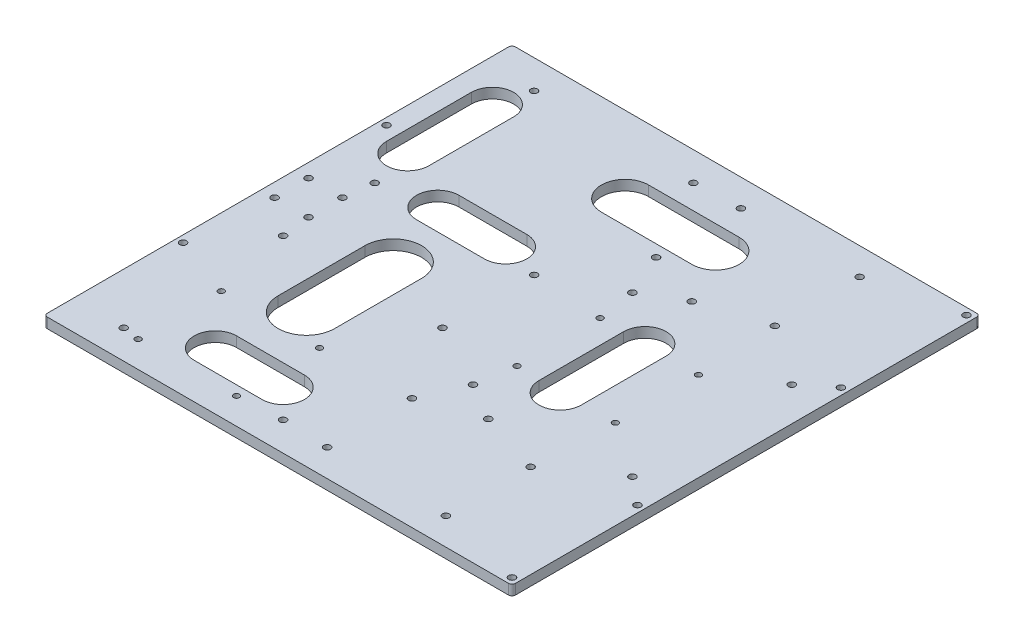
SolidWorks part; units mm, degrees
ref_plane "Спереди" through (0, 0, 0) normal (0, 0, 1) x (1, 0, 0)
ref_plane "Сверху" through (0, 0, 0) normal (0, 1, 0) x (1, 0, 0)
ref_plane "Справа" through (0, 0, 0) normal (1, 0, 0) x (0, 0, -1)
sketch "Эскиз1" plane through (0, 0, 0) normal (0, 1, 0) x (1, 0, 0)
  line L1 (-138, -138) -> (138, -138)
  line L2 (-138, -138) -> (-138, 138)
  line L3 (-138, 138) -> (138, 138)
  line L4 (138, -138) -> (138, 138)
  line L5 (0, 138) -> (0, -138) construction
  line L6 (-138, 0) -> (138, 0) construction
  point P0 (0, 0)
  dimension "D1" = 276
  dimension "D2" = 276
extrude "Бобышка-Вытянуть1" add sketch "Эскиз1" along normal blind 6
fillet "Скругление1" radius 2 4 edges at (138, 3, 138) (-138, 3, 138) (-138, 3, -138) (138, 3, -138)
sketch "Эскиз2" plane through (0, 6, 0) normal (0, 1, 0) x (1, 0, 0)
  line L0 (0, 147.7994) -> (0, 0) construction
  line L1 (0, 0) -> (-164.0684, 0) construction
  line L2 (-164.0684, 0) -> (215.1731, 0) construction
  circle A0 centre (-134, 60) radius 2
  circle A1 centre (134, 60) radius 2
  circle A2 centre (134, -60) radius 2
  circle A3 centre (-134, -60) radius 2
  circle A4 centre (46, 60) radius 2
  circle A5 centre (46, -60) radius 2
  circle A6 centre (134, 134) radius 2
  circle A7 centre (134, -134) radius 2
  dimension "D1" = 134
  dimension "D2" = 60
  dimension "D4" = 134
  dimension "D3" = 46
  dimension "D5" = 134
extrude "Вырез-Вытянуть1" cut sketch "Эскиз2" against normal blind 6
sketch "Эскиз10" plane through (0, 6, 0) normal (0, 1, 0) x (1, 0, 0)
  line L0 (0, 0) -> (99.2175, -171.8497) construction
  line L1 (0, 0) -> (206.3493, 0) construction
  line L2 (13, -97) -> (83, -97) construction
  line L3 (13, 72) -> (83, 72) construction
  line L4 (13, 72) -> (13, 122) construction
  line L5 (13, 122) -> (83, 122) construction
  line L6 (83, 72) -> (83, 122) construction
  line L7 (48, 122) -> (48, 72) construction
  line L8 (13, 97) -> (83, 97) construction
  line L9 (48, -122) -> (48, -72) construction
  line L15 (136, 138) -> (-136, 138) construction
  line L16 (-27.8464, 0) -> (-120, 0) construction
  line L17 (-120, 0) -> (0, 0) construction
  line L19 (-130, -10) -> (-110, -10) construction
  line L20 (-130, -10) -> (-130, 10) construction
  line L21 (-130, 10) -> (-110, 10) construction
  line L22 (-110, -10) -> (-110, 10) construction
  line L23 (-120, 10) -> (-120, -10) construction
  line L24 (-130, 0) -> (-110, 0) construction
  line L25 (0, 0) -> (99.2175, 171.8497) construction
  line L26 (83, -72) -> (83, -122) construction
  line L27 (13, -122) -> (83, -122) construction
  line L28 (13, -72) -> (13, -122) construction
  line L29 (13, -72) -> (83, -72) construction
  line L30 (138, -136) -> (138, 136) construction
  line L32 (138, -138) -> (60, -138) construction
  line L33 (138, -138) -> (138, -103.923) construction
  line L34 (138, -103.923) -> (60, -103.923) construction
  line L35 (60, -138) -> (60, -103.923) construction
  line L36 (83, 122) -> (60, 122) construction
  line L37 (83, 122) -> (83, 103.923) construction
  line L38 (83, 103.923) -> (60, 103.923) construction
  line L39 (60, 122) -> (60, 103.923) construction
  circle A0 centre (13, 122) radius 2
  circle A1 centre (83, 122) radius 2
  circle A2 centre (13, 72) radius 2
  circle A3 centre (83, 72) radius 2
  circle A8 centre (-130, 10) radius 2
  circle A9 centre (-110, 10) radius 2
  circle A10 centre (-110, -10) radius 2
  circle A11 centre (-130, -10) radius 2
  circle A13 centre (0, 0) radius 120 construction
  circle A14 centre (83, -72) radius 2
  circle A15 centre (13, -72) radius 2
  circle A16 centre (83, -122) radius 2
  circle A17 centre (13, -122) radius 2
  point P5 (48, 97)
  point P25 (48, -97)
  dimension "D3" = 4
  dimension "D9" = 23
  dimension "D10" = 18.077
  dimension "D1" = 50
  dimension "D2" = 70
  dimension "D4" = 90
  dimension "D5" = 16
  dimension "D6" = 20
  dimension "D7" = 20
  dimension "D8" = 120
  dimension "D11" = 78
  dimension "D12" = 34.077
extrude "Под стойки и сервы" cut sketch "Эскиз10" against normal blind 7
sketch "Эскиз3" plane through (0, 6, 0) normal (0, 1, 0) x (1, 0, 0)
  line L0 (0, 147.4317) -> (0, 0) construction
  line L1 (-193.8488, 0) -> (193.8488, 0) construction
  line L2 (138, -136) -> (138, 136) construction
  line L7 (43, 82) -> (43, -82) construction
  line L13 (43, 75) -> (43, -75) construction
  line L14 (-117, -82) -> (33, -82) construction
  line L16 (-117, 82) -> (33, 82) construction
  line L18 (-42, 82) -> (-42, -82) construction
  line L19 (-89.5005, 0) -> (60.4995, 0) construction
  line L20 (-124, -75) -> (40, -75) construction
  line L22 (-124, 75) -> (40, 75) construction
  line L24 (-42, 75) -> (-42, -75) construction
  line L25 (-96.5005, 0) -> (67.4995, 0) construction
  circle A0 centre (-32, 82) radius 2
  circle A1 centre (118, 82) radius 2
  circle A2 centre (125, 75) radius 2
  circle A3 centre (-39, 75) radius 2
  circle A4 centre (118, -82) radius 2
  circle A5 centre (125, -75) radius 2
  circle A6 centre (-32, -82) radius 2
  circle A7 centre (-39, -75) radius 2
  circle A8 centre (-124, 75) radius 2
  circle A10 centre (40, 75) radius 2
  circle A11 centre (33, 82) radius 2
  circle A12 centre (40, -75) radius 2
  circle A13 centre (33, -82) radius 2
  circle A14 centre (-117, -82) radius 2
  circle A15 centre (-124, -75) radius 2
  circle A16 centre (-117, 82) radius 2
  point P3 (43, 0)
  point P8 (43, 0)
  point P22 (-42, 0)
  point P24 (-42, 0)
  dimension "D3" = 95
  dimension "D1" = 150
  dimension "D2" = 164
  dimension "D4" = 150
  dimension "D5" = 164
  dimension "D6" = 180
extrude "150х164" [suppressed] cut sketch "Эскиз3" against normal blind 6
sketch "Эскиз7" plane through (0, 6, 0) normal (0, 1, 0) x (1, 0, 0)
  line L0 (-167.0096, 52) -> (194.2165, 52) construction
  line L2 (-18, 26) -> (98, 26) construction
  line L3 (-18, 26) -> (-18, 78) construction
  line L4 (-18, 78) -> (98, 78) construction
  line L5 (98, 26) -> (98, 78) construction
  line L6 (40, 78) -> (40, 26) construction
  line L7 (-18, 52) -> (98, 52) construction
  line L8 (136, 138) -> (-136, 138) construction
  circle A0 centre (-18, 78) radius 1.75
  circle A1 centre (-18, 26) radius 1.75
  circle A2 centre (98, 78) radius 1.75
  circle A3 centre (98, 26) radius 1.75
  point P2 (40, 52)
  dimension "D3" = 3.5
  dimension "D1" = 116
  dimension "D2" = 52
  dimension "D4" = 40
  dimension "D5" = 60
extrude "Jetson" [suppressed] cut sketch "Эскиз7" against normal blind 6
sketch "Эскиз9" plane through (0, 6, 0) normal (0, 1, 0) x (1, 0, 0)
  line L0 (-18.2911, 15.2367) -> (-18.2911, -61.2367) construction
  line L1 (-18.2911, -61.2367) -> (91.6393, -61.2367) construction
  line L2 (91.6393, -61.2367) -> (91.6393, -138) construction
  line L3 (-136, -138) -> (136, -138) construction
  line L4 (91.6393, -138) -> (129.5083, -138) construction
  line L5 (129.5083, -138) -> (129.5083, 138) construction
  line L6 (136, 138) -> (-136, 138) construction
  line L7 (129.5083, 138) -> (112.5959, 138) construction
  line L8 (112.5959, 138) -> (112.5959, 17.8103) construction
  line L9 (112.5959, 17.8103) -> (-18.2911, 17.8103) construction
  line L10 (-18.2911, 17.8103) -> (-18.2911, 15.2367) construction
  line L11 (-18.2911, -23) -> (230.269, -23) construction
  line L12 (138, -136) -> (138, 136) construction
  line L13 (-7, 2) -> (-7, -48) construction
  line L14 (43, 2) -> (43, -48) construction
  line L15 (43, -48) -> (83, -48) construction
  line L16 (83, -48) -> (83, 2) construction
  line L17 (83, 2) -> (123, 2) construction
  line L18 (123, 2) -> (123, -48) construction
  line L19 (98, -17) -> (128, -17) construction
  line L26 (98, -17) -> (98, 13) construction
  line L27 (98, 13) -> (128, 13) construction
  line L28 (128, -17) -> (128, 13) construction
  line L29 (113, 13) -> (113, -17) construction
  line L30 (98, -2) -> (128, -2) construction
  circle A0 centre (-7, 2) radius 1.8
  circle A1 centre (43, 2) radius 1.8
  circle A2 centre (83, 2) radius 1.8
  circle A3 centre (123, 2) radius 1.8
  circle A4 centre (123, -48) radius 1.8
  circle A5 centre (83, -48) radius 1.8
  circle A6 centre (43, -48) radius 1.8
  circle A7 centre (-7, -48) radius 1.8
  circle A8 centre (43, -23) radius 1.8
  circle A9 centre (-7, -23) radius 1.8
  circle A10 centre (83, -23) radius 1.8
  circle A11 centre (123, -23) radius 1.8
  circle A12 centre (123, 62) radius 1.8
  circle A13 centre (123, 122) radius 1.8
  circle A15 centre (123, -108) radius 1.8
  circle A20 centre (98, 13) radius 1.8
  circle A21 centre (128, 13) radius 1.8
  circle A22 centre (98, -17) radius 1.8
  circle A23 centre (128, -17) radius 1.8
  circle A24 centre (98, -29) radius 1.8
  circle A25 centre (128, -29) radius 1.8
  circle A26 centre (128, -59) radius 1.8
  circle A27 centre (98, -59) radius 1.8
  point P61 (113, -2)
  dimension "D1" = 3.6
  dimension "D2" = 50
  dimension "D3" = 40
  dimension "D4" = 40
  dimension "D12" = 30
  dimension "D5" = 25
  dimension "D6" = 60
  dimension "D7" = 60
  dimension "D8" = 115
  dimension "D9" = 15
  dimension "D13" = 30
  dimension "D14" = 10
  dimension "D15" = 140
extrude "Вырез-Вытянуть8" [suppressed] cut sketch "Эскиз9" against normal blind 6
sketch "Эскиз4" plane through (0, 6, 0) normal (0, 1, 0) x (1, 0, 0)
  line L0 (-244.2183, 0) -> (0, 0) construction
  line L1 (0, 0) -> (0, 146.3288) construction
  line L2 (-177.488, 74) -> (64.2486, 74) construction
  line L3 (-138, 136) -> (-138, -136) construction
  line L4 (-108, 27) -> (-14, 27) construction
  line L5 (-108, 27) -> (-108, 121) construction
  line L6 (-108, 121) -> (-14, 121) construction
  line L7 (-14, 27) -> (-14, 121) construction
  line L8 (-61, 121) -> (-61, 27) construction
  line L9 (-108, 74) -> (-14, 74) construction
  line L10 (0, 0) -> (256.1096, 0) construction
  line L11 (24, -47) -> (118, -47) construction
  line L12 (24, -47) -> (24, 47) construction
  line L13 (24, 47) -> (118, 47) construction
  line L14 (118, -47) -> (118, 47) construction
  line L15 (71, 47) -> (71, -47) construction
  line L16 (24, 0) -> (118, 0) construction
  line L17 (138, -136) -> (138, 136) construction
  circle A0 centre (-108, 121) radius 2
  circle A1 centre (-14, 121) radius 2
  circle A2 centre (-14, 27) radius 2
  circle A3 centre (-108, 27) radius 2
  circle A4 centre (-108, -27) radius 2
  circle A5 centre (-14, -27) radius 2
  circle A6 centre (-14, -121) radius 2
  circle A7 centre (-108, -121) radius 2
  circle A8 centre (24, 47) radius 2
  circle A9 centre (118, 47) radius 2
  circle A10 centre (118, -47) radius 2
  circle A11 centre (24, -47) radius 2
  point P6 (-61, 74)
  point P24 (71, 0)
  point P38 (0, 0)
  dimension "D5" = 94
  dimension "D1" = 94
  dimension "D2" = 94
  dimension "D3" = 74
  dimension "D4" = 30
  dimension "D6" = 94
  dimension "D7" = 20
extrude "94х94" cut sketch "Эскиз4" against normal blind 6
sketch "Эскиз8" plane through (0, 6, 0) normal (0, 1, 0) x (1, 0, 0)
  line L1 (27.4655, -24.5) -> (85.4655, -24.5) construction
  line L2 (27.4655, -24.5) -> (27.4655, 24.5) construction
  line L3 (27.4655, 24.5) -> (85.4655, 24.5) construction
  line L4 (85.4655, -24.5) -> (85.4655, 24.5) construction
  line L5 (56.4655, 24.5) -> (56.4655, -24.5) construction
  line L6 (27.4655, 0) -> (85.4655, 0) construction
  line L8 (0, 166.5491) -> (0, 0) construction
  line L9 (0, 0) -> (185.1673, 0) construction
  line L10 (-167.745, -98) -> (174.3629, -98) construction
  line L11 (-98, -122.5) -> (-40, -122.5) construction
  line L12 (-98, -122.5) -> (-98, -73.5) construction
  line L13 (-98, -73.5) -> (-40, -73.5) construction
  line L14 (-40, -122.5) -> (-40, -73.5) construction
  line L15 (-69, -73.5) -> (-69, -122.5) construction
  line L16 (-98, -98) -> (-40, -98) construction
  line L17 (-136, -138) -> (136, -138) construction
  line L18 (-138, 136) -> (-138, -136) construction
  circle A0 centre (85.4655, 24.5) radius 1.75
  circle A1 centre (27.4655, 24.5) radius 1.75
  circle A2 centre (27.4655, -24.5) radius 1.75
  circle A3 centre (85.4655, -24.5) radius 1.75
  circle A4 centre (-40, -73.5) radius 1.75
  circle A5 centre (-98, -73.5) radius 1.75
  circle A6 centre (-98, -122.5) radius 1.75
  circle A7 centre (-40, -122.5) radius 1.75
  point P0 (56.4655, 0)
  point P4 (-69, -98)
  point P26 (0, 0)
  dimension "D5" = 3.5
  dimension "D1" = 58
  dimension "D2" = 49
  dimension "D3" = 40
  dimension "D4" = 40
extrude "RPi4" cut sketch "Эскиз8" against normal blind 6
sketch "Эскиз6" plane through (0, 6, 0) normal (0, 1, 0) x (1, 0, 0)
  line L0 (-70.6279, -104.2964) -> (-30.6279, -104.2964) construction
  line L3 (0, 165.0655) -> (0, 0) construction
  line L4 (0, 0) -> (164.436, 0) construction
  line L5 (-70.6279, -91.7964) -> (-30.6279, -91.7964)
  line L9 (-76.8541, 33.0775) -> (-36.8541, 33.0775) construction
  line L10 (-76.8541, 45.5775) -> (-36.8541, 45.5775)
  line L11 (-76.8541, 20.5775) -> (-36.8541, 20.5775)
  line L13 (-70.6279, -116.7964) -> (-30.6279, -116.7964)
  line L16 (-62.1479, -7.8884) -> (-62.1479, -59.1081) construction
  line L20 (-113.2922, 101.779) -> (-113.2922, 51.779) construction
  line L21 (-125.7922, 101.779) -> (-125.7922, 51.779)
  line L22 (-100.7922, 101.779) -> (-100.7922, 51.779)
  line L23 (-26.2076, 92.8656) -> (27.1824, 92.8656) construction
  line L24 (-26.2076, 106.7739) -> (27.1824, 106.7739)
  line L25 (-26.2076, 78.9573) -> (27.1824, 78.9573)
  line L26 (-78.8638, -7.8884) -> (-78.8638, -59.1081)
  line L29 (-45.4321, -7.8884) -> (-45.4321, -59.1081)
  line L30 (53.8487, 24.5334) -> (53.8487, -25.4666) construction
  line L31 (41.3487, 24.5334) -> (41.3487, -25.4666)
  line L32 (66.3487, 24.5334) -> (66.3487, -25.4666)
  arc A4 (-76.8541, 45.5775) -> (-76.8541, 20.5775) centre (-76.8541, 33.0775) ccw
  arc A5 (-36.8541, 20.5775) -> (-36.8541, 45.5775) centre (-36.8541, 33.0775) ccw
  arc A10 (-125.7922, 101.779) -> (-100.7922, 101.779) centre (-113.2922, 101.779) cw
  arc A11 (-100.7922, 51.779) -> (-125.7922, 51.779) centre (-113.2922, 51.779) cw
  arc A12 (-26.2076, 106.7739) -> (-26.2076, 78.9573) centre (-26.2076, 92.8656) ccw
  arc A13 (27.1824, 78.9573) -> (27.1824, 106.7739) centre (27.1824, 92.8656) ccw
  arc A16 (-70.6279, -91.7964) -> (-70.6279, -116.7964) centre (-70.6279, -104.2964) ccw
  arc A17 (-30.6279, -116.7964) -> (-30.6279, -91.7964) centre (-30.6279, -104.2964) ccw
  arc A18 (-78.8638, -7.8884) -> (-45.4321, -7.8884) centre (-62.1479, -7.8884) cw
  arc A19 (-45.4321, -59.1081) -> (-78.8638, -59.1081) centre (-62.1479, -59.1081) cw
  arc A20 (41.3487, 24.5334) -> (66.3487, 24.5334) centre (53.8487, 24.5334) cw
  arc A21 (66.3487, -25.4666) -> (41.3487, -25.4666) centre (53.8487, -25.4666) cw
  point P2 (-50.6279, -104.2964)
  point P13 (-62.1479, -33.4983)
  point P22 (-56.8541, 33.0775)
  point P27 (-37.5165, -1.3908)
  point P30 (53.8487, -0.4666)
  point P43 (0, 165.0655)
  point P47 (-113.2922, 76.779)
  point P54 (0.4874, 92.8656)
extrude "Вырез-Вытянуть5" cut sketch "Эскиз6" against normal blind 6 contours A11 L22 A10 L21 | L25 A13 L24 A12 | L11 A5 L10 A4 | A19 L29 A18 L26 | A21 L32 A20 L31 | L13 A17 L5 A16 region at (-50.6279, 6, 104.2964) region at (-56.8541, 6, -33.0775) region at (-113.2922, 6, -76.779) region at (0.4874, 6, -92.8656) region at (-62.1479, 6, 33.4983) region at (53.8487, 6, 0.4666)
